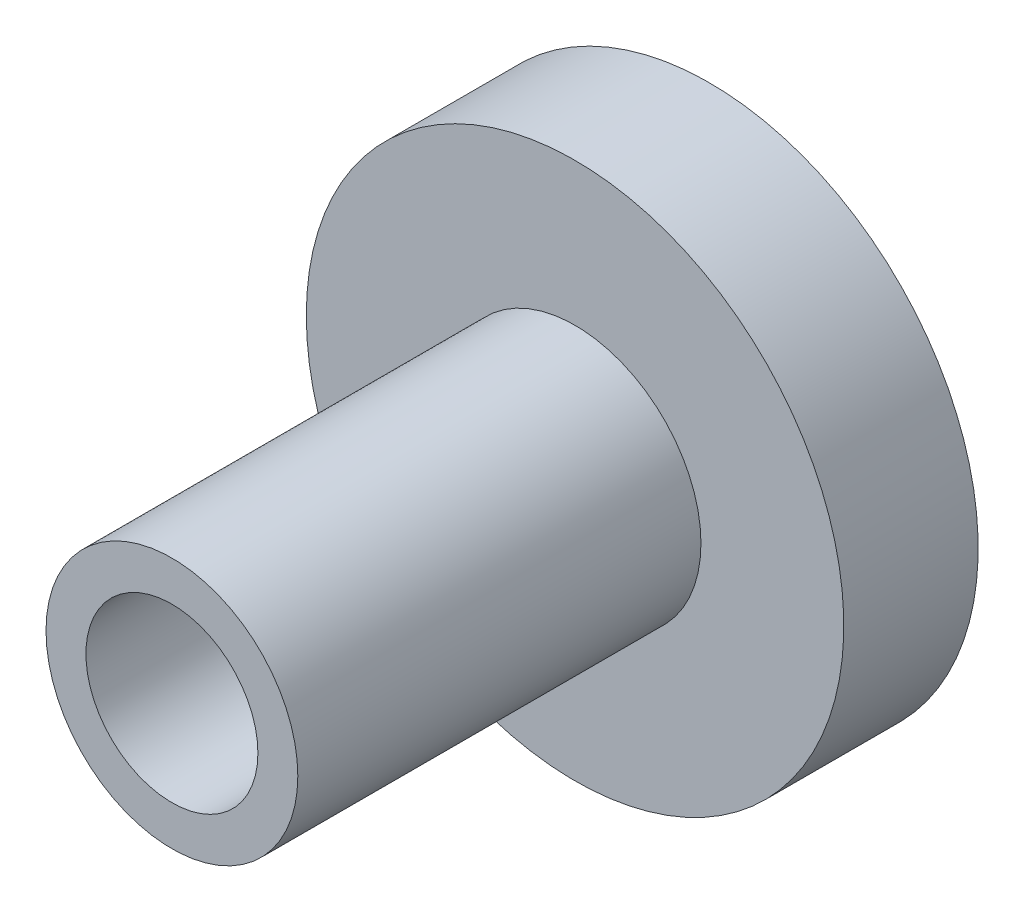
SolidWorks part; units mm, degrees
ref_plane "Front Plane" through (0, 0, 0) normal (0, 0, 1) x (1, 0, 0)
ref_plane "Top Plane" through (0, 0, 0) normal (0, 1, 0) x (1, 0, 0)
ref_plane "Right Plane" through (0, 0, 0) normal (1, 0, 0) x (0, 0, -1)
sketch "Sketch1" plane through (0, 0, 0) normal (0, 0, 1) x (1, 0, 0)
  circle A0 centre (0, 0) radius 5.95
  dimension "D1" = 11.9
extrude "Boss-Extrude1" add sketch "Sketch1" along normal blind 19.05
sketch "Sketch2" plane through (0, 0, 0) normal (0, 0, -1) x (-1, 0, 0)
  circle A0 centre (0, 0) radius 12.7
  dimension "D1" = 25.4
extrude "Boss-Extrude2" add sketch "Sketch2" along normal blind 6.35
sketch "Sketch3" plane through (0, 0, 19.05) normal (0, 0, 1) x (1, 0, 0)
  circle A0 centre (0, 0) radius 4.064
  dimension "D1" = 8.128
extrude "Cut-Extrude1" cut sketch "Sketch3" against normal offset from surface (15.875 mm away) 3.175 up to face at (5.95, 0, 0)
hole_wizard "CSK for #8 Flat Head Machine Screw (100)1" positions "Sketch4" profile "Sketch6" countersink size "#8" standard "ANSI Inch" end condition up to next
sketch "Sketch4" plane through (0, 0, 3.175) normal (0, 0, 1) x (1, 0, 0)
  point P0 (0, 0)
sketch "Sketch6" plane through (0, 0, 3.175) normal (1, 0, 0) x (0, -1, 0)
  line L0 (0, 0) -> (0, 9.525)
  line L1 (0, 9.525) -> (2.2479, 9.525)
  line L2 (2.2479, 9.525) -> (2.2479, 1.6518)
  line L3 (2.2479, 1.6518) -> (4.2164, 0)
  line L5 (4.2164, 0) -> (0, 0)
  line L6 (-2.2479, 1.6518) -> (-4.2164, 0) construction
  line L11 (0, -6.35) -> (0, 107.95) construction
  dimension "Thru Hole Dia." = 4.4958
  dimension "Thru Hole Depth" = 9.525
  dimension "Near C'Sink Dia." = 8.4328
  dimension "Near C'Sink Angle" = 100
sketch "Sketch7" plane through (0, 0, 3.175) normal (0, 0, -1) x (-1, 0, 0)
  circle A0 centre (0, 0) radius 4.064 construction
  circle A1 centre (0, 0) radius 4.2164
  circle A2 centre (0, 0) radius 4.2164
  circle A3 centre (0, 0) radius 4.064
  dimension "D1" = 0
extrude "Boss-Extrude3" add sketch "Sketch7" along normal up to surface up to face at (2.2479, 0, 1.5232)
sketch "Sketch8" plane through (0, 0, -6.35) normal (0, 0, -1) x (-1, 0, 0)
  line L1 (2.5297, -4.3815) -> (5.0593, 0)
  line L2 (5.0593, 0) -> (2.5297, 4.3815)
  line L3 (2.5297, 4.3815) -> (-2.5297, 4.3815)
  line L4 (-2.5297, 4.3815) -> (-5.0593, 0)
  line L5 (-5.0593, 0) -> (-2.5297, -4.3815)
  line L6 (-2.5297, -4.3815) -> (2.5297, -4.3815)
  circle A0 centre (0, 0) radius 4.3815 construction
  dimension "D1" = 8.763
extrude "Cut-Extrude2" cut sketch "Sketch8" against normal blind 4.7625
other "Move Face1" flip direction yes face at (3.7945, 2.1907, -3.9688) face at (0, 4.3815, -3.9688) face at (-3.7945, 2.1908, -3.9688) face at (-3.7945, -2.1907, -3.9688) face at (0, -4.3815, -3.9688) face at (3.7945, -2.1907, -3.9688) offset 0.254 parameters "D1"=0.254
sketch "Sketch10" plane through (0, 0, 19.05) normal (0, 0, 1) x (1, 0, 0)
  line L0 (-5.1383, -3) -> (-5.1383, 3)
  circle A0 centre (0, 0) radius 5.95 construction
  dimension "D1" = 6
ref_plane "Plane2" through (-5.1383, 0, 0) normal (1, 0, 0) x (0, 1, 0)
sketch "Sketch9" plane through (-5.1383, 0, 0) normal (-1, 0, 0) x (0, 0, 1)
  line L0 (0, -5.95) -> (0, 5.95) construction
  line L1 (12, 3) -> (6, 3)
  line L2 (12, 3) -> (12, -3)
  line L3 (12, -3) -> (6, -3)
  line L4 (6, 3) -> (6, -3)
  line L5 (12, 3) -> (6, -3) construction
  line L6 (12, -3) -> (6, 3) construction
  point P0 (9, 0)
  point P10 (0, 0)
  dimension "D1" = 6
  dimension "D2" = 6
  dimension "D3" = 6
extrude "Cut-Extrude3" cut sketch "Sketch9" along normal through all
draft "Draft1" type of draft neutral plane draft angle 65 faces to draft 2 face at (-5.5442, 0, 12) face at (-5.5442, 0, 6) neutral plane through (-5.1383, 0, 0) neutral plane normal (-1, 0, 0) parameters "D1"=65
